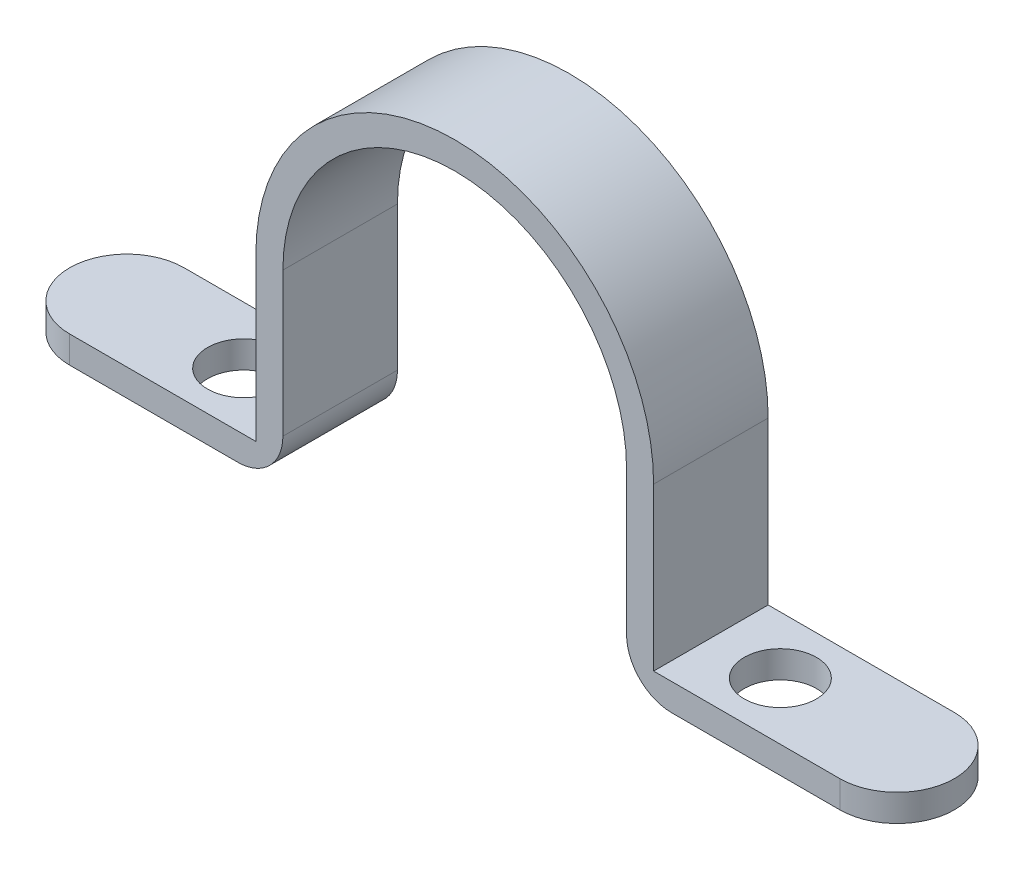
SolidWorks part; units mm, degrees
ref_plane "Front Plane" through (0, 0, 0) normal (0, 0, 1) x (1, 0, 0)
ref_plane "Top Plane" through (0, 0, 0) normal (0, 1, 0) x (1, 0, 0)
ref_plane "Right Plane" through (0, 0, 0) normal (1, 0, 0) x (0, 0, -1)
sketch "Sketch1" plane through (0, 0, 0) normal (0, 0, 1) x (1, 0, 0)
  line L0 (-45.221, 0) -> (-18.221, 0)
  line L1 (-18.221, 0) -> (-18.221, 40)
  line L2 (-18.221, 40) -> (25.879, 40)
  line L3 (25.879, 40) -> (25.879, 0)
  line L4 (25.879, 0) -> (52.879, 0)
  line L5 (-45.221, -3) -> (-15.221, -3)
  line L6 (-15.221, -3) -> (-15.221, 37)
  line L7 (-15.221, 37) -> (22.879, 37)
  line L8 (22.879, 37) -> (22.879, -3)
  line L9 (22.879, -3) -> (52.879, -3)
  line L10 (-45.221, 0) -> (-45.221, -3)
  line L11 (52.879, 0) -> (52.879, -3)
  dimension "D1" = 40
  dimension "D2" = 3
  dimension "D3" = 30
  dimension "D4" = 30
  dimension "D5" = 38.1
extrude "Boss-Extrude1" add sketch "Sketch1" along normal blind 12.7
fillet "Fillet1" 2 edges at (-15.221, 37, 6.35) (22.879, 37, 6.35) type full round first side face at (-15.221, 17, 6.35) second side face at (22.879, 17, 6.35) middle face at (3.829, 37, 6.35)
fillet "Fillet4" 2 edges at (-18.221, 40, 6.35) (25.879, 40, 6.35) type full round first side face at (-18.221, 20, 6.35) second side face at (25.879, 20, 6.35) middle face at (3.829, 40, 6.35)
sketch "Sketch2" plane through (0, 0, 0) normal (0, 1, 0) x (1, 0, 0)
  line L0 (-18.221, -12.7) -> (-18.221, 0) construction
  line L1 (25.879, -12.7) -> (25.879, 0) construction
  circle A0 centre (-25.921, -6.35) radius 4
  circle A1 centre (33.579, -6.35) radius 4
  point P8 (33.579, -6.35)
  dimension "D1" = 8
  dimension "D5" = 8
  dimension "D2" = 7.7
  dimension "D3" = 7.7
  dimension "D4" = 59.5
extrude "Cut-Extrude1" cut sketch "Sketch2" against normal through all
fillet "Fillet5" 2 edges at (-45.221, -1.5, 12.7) (-45.221, -1.5, 0) type full round first side face at (3.829, 8.4083, 12.7) second side face at (3.829, 8.4083, 0) middle face at (-45.221, -1.5, 6.35)
fillet "Fillet6" 2 edges at (52.879, -1.5, 12.7) (52.879, -1.5, 0) type full round first side face at (4.8874, 8.4083, 12.7) second side face at (4.8874, 8.4083, 0) middle face at (52.879, -1.5, 6.35)
fillet "Fillet7" radius 5 2 edges at (-15.221, -3, 6.35) (22.879, -3, 6.35)
